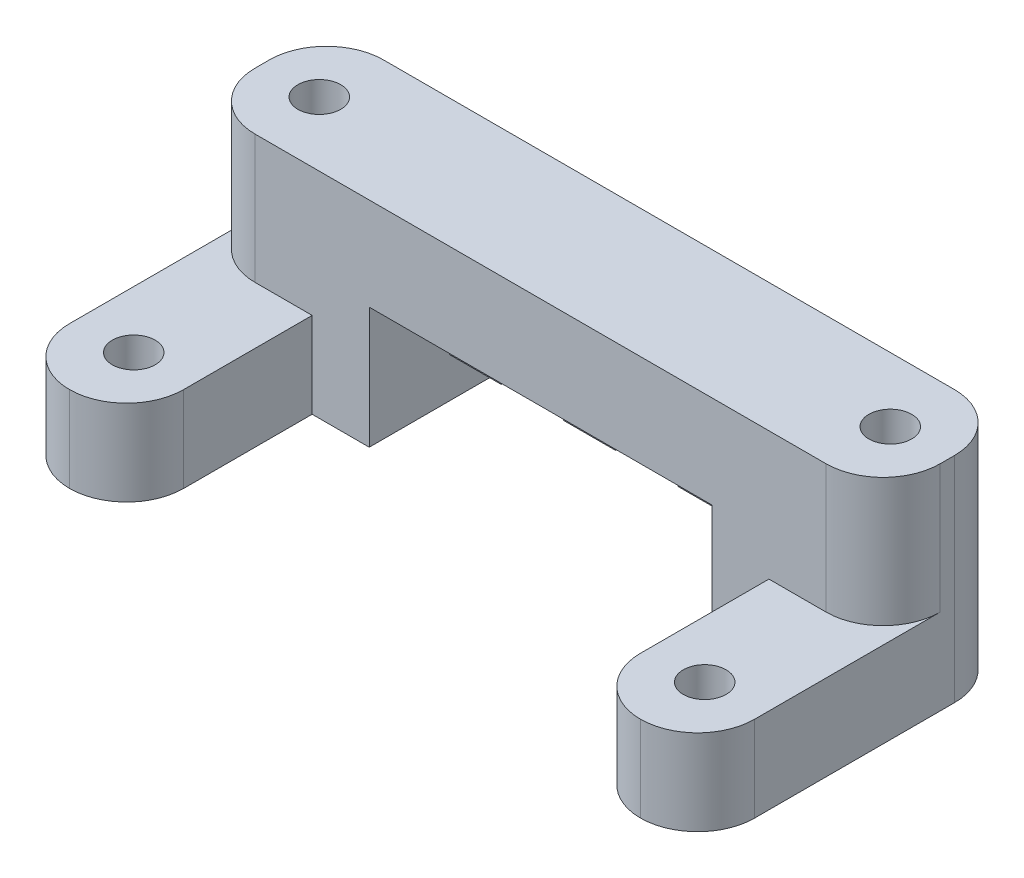
SolidWorks part; units mm, degrees
ref_plane "Front Plane" through (0, 0, 0) normal (0, 0, 1) x (1, 0, 0)
ref_plane "Top Plane" through (0, 0, 0) normal (0, 1, 0) x (1, 0, 0)
ref_plane "Right Plane" through (0, 0, 0) normal (1, 0, 0) x (0, 0, -1)
sketch "Sketch1" plane through (0, 0, 0) normal (0, 0, 1) x (1, 0, 0)
  line L0 (0, 0) -> (12, 0)
  line L1 (12, 0) -> (12, 8.5)
  line L2 (12, 8.5) -> (36, 8.5)
  line L3 (36, 8.5) -> (36, 0)
  line L4 (36, 0) -> (48, 0)
  line L5 (48, 0) -> (48, 15)
  line L8 (48, 15) -> (0, 15)
  line L11 (0, 15) -> (0, 0)
  point P3 (24, 8.5)
  point P8 (0, 14.0609)
  point P9 (0, 10.5048)
  point P12 (50, 14.0609)
  point P13 (24, 15)
  dimension "D1" = 8.5
  dimension "D2" = 24
  dimension "D3" = 12
  dimension "D4" = 15
extrude "Boss-Extrude1" add sketch "Sketch1" along normal blind 9
sketch "Sketch2" plane through (0, 8.5, 0) normal (0, -1, 0) x (-1, 0, 0)
  line L0 (-12, -9) -> (-12, 0) construction
  line L1 (-14, -5.75) -> (-18, -5.75)
  line L2 (-14, -5.75) -> (-14, -3.25)
  line L3 (-14, -3.25) -> (-18, -3.25)
  line L4 (-18, -5.75) -> (-18, -3.25)
  line L5 (-22, -5.75) -> (-26, -5.75)
  line L6 (-22, -5.75) -> (-22, -3.25)
  line L7 (-22, -3.25) -> (-26, -3.25)
  line L8 (-26, -5.75) -> (-26, -3.25)
  line L9 (-30, -5.75) -> (-34, -5.75)
  line L10 (-30, -5.75) -> (-30, -3.25)
  line L11 (-30, -3.25) -> (-34, -3.25)
  line L12 (-34, -5.75) -> (-34, -3.25)
  point P12 (-16, -5.75)
  point P13 (-24, -5.75)
  point P14 (-32, -5.75)
  point P15 (-34, -4.5)
  point P16 (-26, -4.5)
  point P17 (-18, -4.5)
  point P20 (-12, -4.5)
  point P21 (-14, -4.5)
  dimension "D1" = 4
  dimension "D2" = 2.5
  dimension "D3" = 4
  dimension "D4" = 2.5
  dimension "D5" = 4
  dimension "D6" = 2.5
  dimension "D7" = 8
  dimension "D8" = 8
  dimension "D9" = 4
extrude "Boss-Extrude2" add sketch "Sketch2" along normal blind 3.5 draft 3
sketch "Sketch4" plane through (0, 0, 9) normal (0, 0, 1) x (1, 0, 0)
  line L1 (0, 0) -> (8, 0)
  line L2 (0, 0) -> (0, 6)
  line L3 (0, 6) -> (8, 6)
  line L4 (8, 0) -> (8, 6)
  line L5 (48, 0) -> (40, 0)
  line L6 (48, 0) -> (48, 6)
  line L7 (48, 6) -> (40, 6)
  line L8 (40, 0) -> (40, 6)
  dimension "D1" = 6
  dimension "D2" = 8
  dimension "D3" = 8
extrude "Boss-Extrude4" add sketch "Sketch4" along normal blind 13
sketch "Sketch3" plane through (0, 15, 0) normal (0, 1, 0) x (1, 0, 0)
  line L2 (8, -22) -> (0, -22) construction
  circle A0 centre (4, -4.5) radius 1.5
  circle A1 centre (44, -4.5) radius 1.5
  circle A2 centre (4, -17.5) radius 1.5
  circle A3 centre (44, -17.5) radius 1.5
  point P5 (0, 0)
  point P9 (4, -22)
  point P14 (0, 0)
  point P15 (0, 0)
  point P16 (0, 0)
  point P17 (0, 0)
  dimension "D2" = 3
  dimension "D1" = 40
  dimension "D3" = 13
extrude "Cut-Extrude1" cut sketch "Sketch3" against normal through all
fillet "Fillet1" radius 4 8 edges at (40, 3, 22) (48, 3, 22) (48, 7.5, 0) (48, 10.5, 9) (0, 3, 22) (8, 3, 22) (0, 7.5, 0) (0, 10.5, 9)
